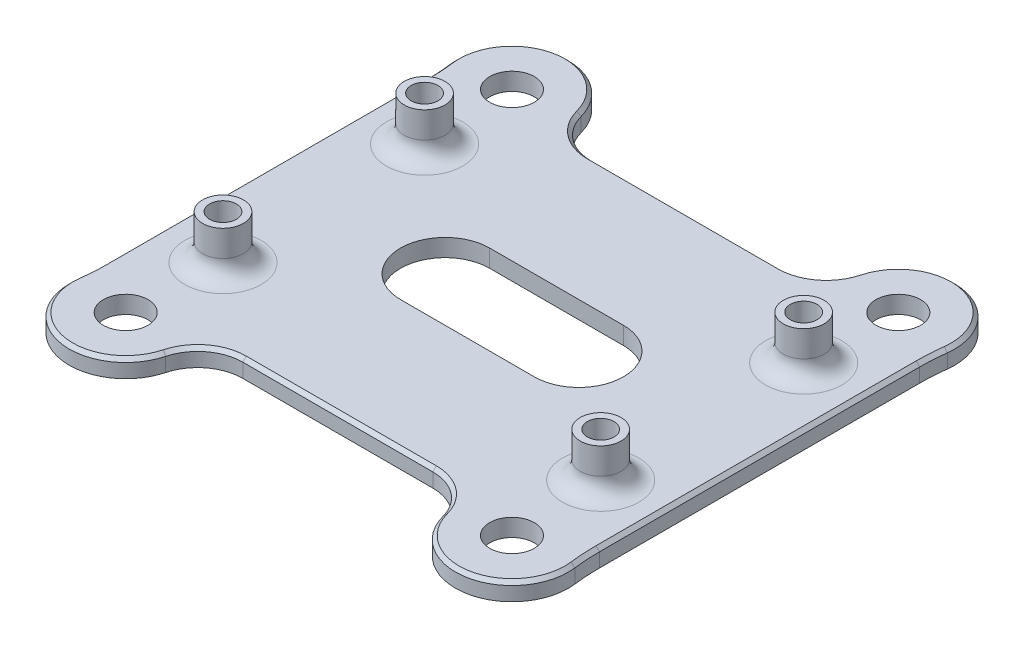
SolidWorks part; units mm, degrees
ref_plane "Front Plane" through (0, 0, 0) normal (0, 0, 1) x (1, 0, 0)
ref_plane "Top Plane" through (0, 0, 0) normal (0, 1, 0) x (1, 0, 0)
ref_plane "Right Plane" through (0, 0, 0) normal (1, 0, 0) x (0, 0, -1)
sketch "Sketch2" plane through (0, 0, 0) normal (0, 1, 0) x (1, 0, 0)
  line L2 (-30.1625, -17.7165) -> (-30.1625, 17.7165)
  line L16 (-30.1625, 17.7165) -> (30.1625, 17.7165)
  line L22 (-30.1625, -17.7165) -> (30.1625, -17.7165)
  line L28 (30.1625, 17.7165) -> (30.1625, -17.7165)
  circle A0 centre (26.9875, 14.5415) radius 1.905
  circle A1 centre (26.9875, -14.3646) radius 1.905
  circle A2 centre (-26.9875, 14.5415) radius 1.905
  circle A3 centre (-26.7335, -14.4145) radius 1.905
  point P5 (-30.1625, 0)
  point P6 (0, 0)
  point P7 (0, 0)
  point P8 (0, 0)
  point P9 (0, -17.7165)
  point P10 (0, 0)
  dimension "D7" = 3.175
  dimension "D13" = 3.81
  dimension "D5" = 3.81
  dimension "D6" = 3.81
  dimension "D14" = 3.81
  dimension "D2" = 60.325
  dimension "D3" = 3.175
  dimension "D4" = 3.175
  dimension "D8" = 3.302
  dimension "D9" = 3.429
  dimension "D10" = 3.3519
  dimension "D11" = 3.175
  dimension "D12" = 3.175
  dimension "D15" = 35.433
extrude "Boss-Extrude1" add sketch "Sketch2" along normal blind 2.5
sketch "Sketch4" plane through (0, 2.5, 0) normal (0, 1, 0) x (1, 0, 0)
  circle A0 centre (-26.9875, 14.5415) radius 2.905
  circle A1 centre (26.9875, 14.5415) radius 2.905
  circle A2 centre (26.9875, -14.3646) radius 2.905
  circle A3 centre (-26.7335, -14.4145) radius 2.905
  circle A4 centre (-26.9875, 14.5415) radius 1.905
  circle A5 centre (26.9875, 14.5415) radius 1.905
  circle A6 centre (26.9875, -14.3646) radius 1.905
  circle A7 centre (-26.7335, -14.4145) radius 1.905
  dimension "D1" = 1
  dimension "D5" = 3.81
extrude "Boss-Extrude3" add sketch "Sketch4" along normal blind 5
sketch "Sketch6" plane through (0, 7.5, 0) normal (0, 1, 0) x (1, 0, 0)
  circle A8 centre (-26.7335, -14.4145) radius 2.905 construction
  circle A9 centre (26.9875, -14.3646) radius 2.905 construction
  circle A10 centre (26.9875, 14.5415) radius 2.905 construction
  circle A11 centre (-26.9875, 14.5415) radius 2.905 construction
  circle A12 centre (-26.7335, -14.4145) radius 2.905
  circle A13 centre (26.9875, -14.3646) radius 2.905
  circle A14 centre (26.9875, 14.5415) radius 2.905
  circle A15 centre (-26.9875, 14.5415) radius 2.905
  circle A16 centre (-26.9875, 14.5415) radius 1.905 construction
  circle A17 centre (-26.7335, -14.4145) radius 1.905 construction
  circle A18 centre (26.9875, -14.3646) radius 1.905 construction
  circle A19 centre (26.9875, 14.5415) radius 1.905 construction
  circle A20 centre (26.9875, 14.5415) radius 1.905
  circle A21 centre (26.9875, -14.3646) radius 1.905
  circle A22 centre (-26.7335, -14.4145) radius 1.905
  circle A23 centre (-26.9875, 14.5415) radius 1.905
extrude "Boss-Extrude4" add sketch "Sketch6" along normal blind 1.27
sketch "Sketch7" plane through (0, 2.5, 0) normal (0, 1, 0) x (1, 0, 0)
  line L1 (-35.2425, 22.7965) -> (35.2425, 22.7965)
  line L2 (-30.1625, -17.7165) -> (30.1625, -17.7165) construction
  line L4 (-35.2425, 22.7965) -> (-35.2425, -22.7965)
  line L5 (-35.2425, -22.7965) -> (35.2425, -22.7965)
  line L6 (35.2425, 22.7965) -> (35.2425, -22.7965)
  line L7 (-30.1625, 17.7165) -> (-30.1625, -17.7165) construction
  line L8 (30.1625, -17.7165) -> (30.1625, 17.7165) construction
  line L10 (-30.1625, 17.7165) -> (30.1625, 17.7165)
  line L11 (-30.1625, 17.7165) -> (-30.1625, -17.7165)
  line L12 (-30.1625, -17.7165) -> (30.1625, -17.7165)
  line L13 (30.1625, 17.7165) -> (30.1625, -17.7165)
  dimension "D1" = 5.08
  dimension "D2" = 5.08
  dimension "D3" = 5.08
  dimension "D4" = 5.08
extrude "Boss-Extrude5" add sketch "Sketch7" against normal up to surface (2.5 mm away) up to face at (-26.9875, 0, -12.6365)
fillet "Fillet5" radius 2.54 1 edges at (-26.9875, 2.5, -17.4465)
fillet "Fillet7" radius 2.54 1 edges at (-26.7335, 2.5, 11.5095)
fillet "Fillet8" radius 2.54 1 edges at (26.9875, 2.5, 11.4596)
fillet "Fillet9" radius 2.54 1 edges at (26.9875, 2.5, -17.4465)
sketch "Sketch8" plane through (0, 0, 0) normal (0, -1, 0) x (1, 0, 0)
  line L0 (-13.53, 24.7965) -> (13.53, 24.7965)
  line L1 (-27.5, 27.5) -> (27.5, 27.5) construction
  line L2 (-27.5, 27.5) -> (-27.5, -27.5) construction
  line L3 (-27.5, -27.5) -> (27.5, -27.5) construction
  line L4 (27.5, 27.5) -> (27.5, -27.5) construction
  line L6 (0, -4.125) -> (0, 4.125) construction
  line L8 (4.125, 0) -> (-4.125, 0) construction
  line L9 (-13.53, -24.7965) -> (13.53, -24.7965)
  line L10 (35.2425, 22.7965) -> (35.2425, -22.7965) construction
  line L11 (35.2425, 22.7965) -> (35.2425, -22.7965)
  line L12 (-35.2425, -22.7965) -> (-35.2425, 22.7965) construction
  line L13 (-35.2425, -22.7965) -> (-35.2425, 22.7965)
  line L14 (-35.2425, 22.7965) -> (35.2425, 22.7965) construction
  circle A0 centre (-27.5, 27.5) radius 3.175
  circle A1 centre (27.5, 27.5) radius 3.175
  circle A2 centre (27.5, -27.5) radius 3.175
  circle A3 centre (-27.5, -27.5) radius 3.175
  arc A4 (-35.4721, 26.5105) -> (-19.7372, 29.5671) centre (-27.5, 27.5) cw
  arc A5 (-19.7372, 29.5671) -> (-13.53, 24.7965) centre (-13.53, 31.22) ccw
  arc A6 (19.7372, 29.5671) -> (13.53, 24.7965) centre (13.53, 31.22) cw
  arc A7 (35.4721, 26.5105) -> (19.7372, 29.5671) centre (27.5, 27.5) ccw
  arc A8 (19.7372, -29.5671) -> (13.53, -24.7965) centre (13.53, -31.22) ccw
  arc A9 (35.4721, -26.5105) -> (19.7372, -29.5671) centre (27.5, -27.5) cw
  arc A10 (-19.7372, -29.5671) -> (-13.53, -24.7965) centre (-13.53, -31.22) cw
  arc A11 (-35.4721, -26.5105) -> (-19.7372, -29.5671) centre (-27.5, -27.5) ccw
  circle A12 centre (-26.7335, 14.4145) radius 1.905 construction
  circle A13 centre (26.9875, 14.3646) radius 1.905 construction
  circle A14 centre (-26.9875, -14.5415) radius 1.905 construction
  circle A15 centre (26.9875, -14.5415) radius 1.905 construction
  circle A16 centre (-26.9875, -14.5415) radius 1.905
  circle A17 centre (-26.7335, 14.4145) radius 1.905
  circle A18 centre (26.9875, 14.3646) radius 1.905
  circle A19 centre (26.9875, -14.5415) radius 1.905
  arc A20 (35.4721, 26.5105) -> (35.2425, 22.7965) centre (65.3931, 22.7965) ccw
  arc A21 (35.4721, -26.5105) -> (35.2425, -22.7965) centre (65.3931, -22.7965) cw
  arc A22 (-35.4721, -26.5105) -> (-35.2425, -22.7965) centre (-65.3931, -22.7965) ccw
  arc A23 (-35.4721, 26.5105) -> (-35.2425, 22.7965) centre (-65.3931, 22.7965) cw
  point P8 (27.5, 0)
  point P9 (0, -27.5)
  point P14 (0, 0)
  point P21 (0, 24.7965)
  point P28 (0, 0)
  point P35 (36.7799, 26.904)
  point P47 (0, 0)
  point P49 (0, 0)
  point P51 (33.9716, 24.3003)
  point P55 (17.8696, 26.1074)
  point P59 (26.9875, 35.0567)
  point P60 (35.8519, 28.7996)
  point P61 (0, 33.772)
  point P62 (-22.3639, 33.772)
  point P63 (-26.7335, 35.0567)
  point P64 (-35.8519, 22.7965)
  dimension "D2" = 6.35
  dimension "D3" = 2
  dimension "D1" = 55
extrude "Boss-Extrude6" add sketch "Sketch8" against normal up to surface (2.5 mm away) up to face at (26.9875, 2.5, -19.9865)
chamfer "Chamfer1" distance 0.5 angle 45 16 edges at (17.4444, 2.5, -26.1269) (0, 2.5, -24.7965) (29.0319, 2.5, -35.3859) (-17.4444, 2.5, -26.1269) (35.3, 2.5, -24.657) (-29.0319, 2.5, -35.3859) (35.2425, 2.5, 0) (-35.3, 2.5, -24.657) (35.3, 2.5, 24.657) (-35.2425, 2.5, 0) (29.0319, 2.5, 35.3859) (-35.3, 2.5, 24.657) (17.4444, 2.5, 26.1269) (-29.0319, 2.5, 35.3859) (0, 2.5, 24.7965) (-17.4444, 2.5, 26.1269)
sketch "Sketch9" plane through (0, 2.5, 0) normal (0, 1, 0) x (1, 0, 0)
  line L0 (-9.525, 0) -> (9.525, 0) construction
  line L1 (-9.525, 6.35) -> (9.525, 6.35)
  line L2 (-9.525, -6.35) -> (9.525, -6.35)
  arc A0 (-9.525, 6.35) -> (-9.525, -6.35) centre (-9.525, 0) ccw
  arc A1 (9.525, -6.35) -> (9.525, 6.35) centre (9.525, 0) ccw
  point P2 (0, 0)
  dimension "D2" = 19.05
  dimension "D1" = 12.7
extrude "Cut-Extrude1" cut sketch "Sketch9" against normal up to surface (2.5 mm away) up to face at (-26.9875, 0, -12.6365)
